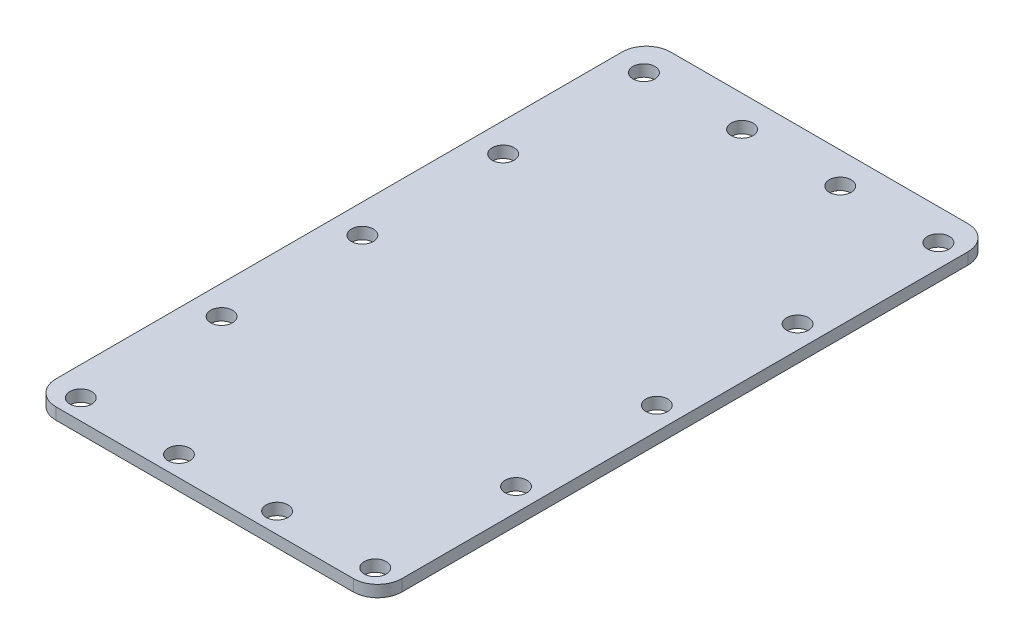
SolidWorks part; units mm, degrees
material "AISI 1020"
ref_plane "Plano frontal" through (0, 0, 0) normal (0, 0, 1) x (1, 0, 0)
ref_plane "Plano superior" through (0, 0, 0) normal (0, 1, 0) x (1, 0, 0)
ref_plane "Plano direito" through (0, 0, 0) normal (1, 0, 0) x (0, 0, -1)
sketch "Esboço1" plane through (0, 0, 0) normal (0, 1, 0) x (1, 0, 0)
  line L0 (-59.3237, 113.6324) -> (-18.9237, 113.6324) construction
  line L1 (-61.2, -126.5) -> (61.2, -126.5)
  line L2 (-71.2, -116.5) -> (-71.2, 116.5)
  line L3 (-61.2, 126.5) -> (61.2, 126.5)
  line L4 (71.2, -116.5) -> (71.2, 116.5)
  line L5 (-71.2, -126.5) -> (71.2, 126.5) construction
  line L6 (-71.2, 126.5) -> (71.2, -126.5) construction
  line L7 (-59.3237, -118.1676) -> (61.8763, -118.1676) construction
  line L8 (-59.3237, -118.1676) -> (-59.3237, 113.6324) construction
  line L13 (-18.9237, 113.6324) -> (21.4763, 113.6324) construction
  line L14 (21.4763, 113.6324) -> (61.8763, 113.6324) construction
  line L15 (61.8763, 113.6324) -> (61.8763, 55.6824) construction
  line L16 (61.8763, 55.6824) -> (61.8763, -2.2676) construction
  line L17 (61.8763, -2.2676) -> (61.8763, -60.2176) construction
  line L18 (61.8763, -60.2176) -> (61.8763, -118.1676) construction
  line L19 (1.2763, -118.1676) -> (1.2763, 113.6324) construction
  line L20 (1.2763, -2.2676) -> (61.8763, -2.2676) construction
  arc A0 (-61.2, 126.5) -> (-71.2, 116.5) centre (-61.2, 116.5) ccw
  arc A1 (-71.2, -116.5) -> (-61.2, -126.5) centre (-61.2, -116.5) ccw
  arc A2 (61.2, -126.5) -> (71.2, -116.5) centre (61.2, -116.5) ccw
  arc A3 (71.2, 116.5) -> (61.2, 126.5) centre (61.2, 116.5) ccw
  circle A6 centre (-59.3237, 113.6324) radius 4.5
  circle A7 centre (61.8763, 113.6324) radius 4.5
  circle A8 centre (-59.3237, -118.1676) radius 4.5
  circle A9 centre (61.8763, -118.1676) radius 4.5
  circle A10 centre (-18.9237, 113.6324) radius 4.5
  circle A11 centre (21.4763, 113.6324) radius 4.5
  circle A12 centre (61.8763, 55.6824) radius 4.5
  circle A13 centre (61.8763, -2.2676) radius 4.5
  circle A14 centre (61.8763, -60.2176) radius 4.5
  circle A15 centre (21.4763, -118.1676) radius 4.5
  circle A16 centre (-18.9237, -118.1676) radius 4.5
  circle A17 centre (-59.3237, -60.2176) radius 4.5
  circle A18 centre (-59.3237, -2.2676) radius 4.5
  circle A19 centre (-59.3237, 55.6824) radius 4.5
  point P0 (0, 0)
  point P18 (1.2763, -2.2676)
  dimension "D3" = 10
  dimension "D6" = 9
  dimension "D1" = 253
  dimension "D2" = 142.4
  dimension "D4" = 121.2
  dimension "D5" = 231.8
base flange "Flange-base1" sketch "Esboço1" thickness 4.8 reverse thickness direction no parameters "D1"=0.7366
sketch "Curva-Linhas1" [suppressed] plane through (0, 0, 0) normal (0, 1, 0) x (1, 0, 0)
sketch "Caixa delimitadora1" [suppressed] plane through (0, 0, 0) normal (0, 1, 0) x (1, 0, 0)
sheet metal parameters "Chapa metálica1" thickness 4.8 parameters "D1"=0.7366
flat pattern "Padrão-Plano1" [suppressed]
sketch "Curva-Linhas2" plane through (0, 0, 0) normal (0, 1, 0) x (1, 0, 0)
sketch3d "Caixa delimitadora2" [suppressed]
  line L0 (10, 10, 0) -> (10, -243, 0) construction
  line L1 (-132.4, 10, 0) -> (-132.4, -243, 0) construction
  line L2 (10, 10, 0) -> (-132.4, 10, 0) construction
  line L3 (10, -243, 0) -> (-132.4, -243, 0) construction
